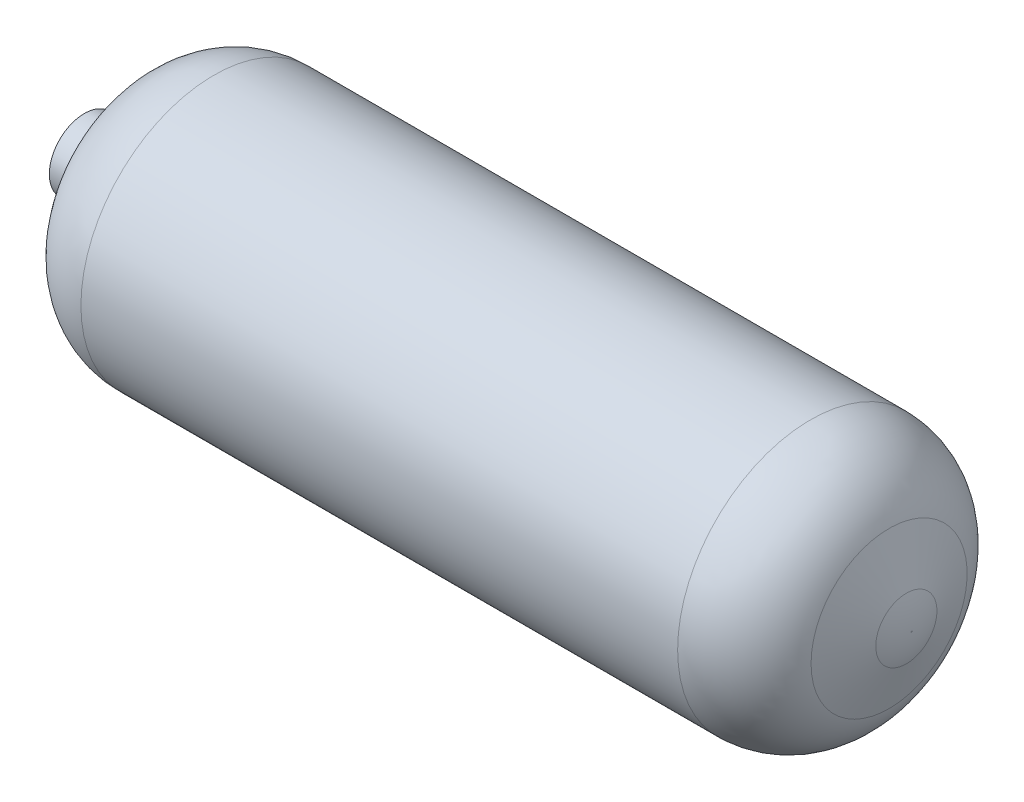
SolidWorks part; units mm, degrees
material "6061-T6 (SS)"
ref_plane "Front Plane" through (0, 0, 0) normal (0, 0, 1) x (1, 0, 0)
ref_plane "Top Plane" through (0, 0, 0) normal (0, 1, 0) x (1, 0, 0)
ref_plane "Right Plane" through (0, 0, 0) normal (1, 0, 0) x (0, 0, -1)
sketch "Sketch1" plane through (0, 0, 0) normal (0, 0, 1) x (1, 0, 0)
  line L0 (-0.2756, 0.129) -> (0.3032, 0.129)
  line L1 (-0.4012, 0.034) -> (-0.4012, 0)
  line L2 (-0.4012, 0.034) -> (-0.3773, 0.034)
  line L4 (-0.3729, 0.0367) -> (-0.3487, 0.0842)
  line L5 (-0.4012, 0) -> (0.4012, 0) construction
  line L6 (0.3794, 0.0757) -> (0.3961, 0.0297)
  line L7 (-0.4012, 0) -> (0.4012, 0)
  line L8 (0.4012, 0) -> (0.4012, 0.0006)
  arc A0 (-0.2756, 0.129) -> (-0.3487, 0.0842) centre (-0.2756, 0.047) ccw
  arc A1 (0.3032, 0.129) -> (0.3794, 0.0757) centre (0.3032, 0.048) cw
  arc A2 (0.4012, 0.0006) -> (0.3961, 0.0297) centre (0.3163, 0.0006) ccw
  arc A3 (-0.3729, 0.0367) -> (-0.3773, 0.034) centre (-0.3773, 0.039) cw
  point P6 (-0.3742, 0.034)
  dimension "D8" = 0.082
  dimension "D11" = 0.081
  dimension "D13" = 0.085
  dimension "D6" = 0.005
  dimension "D2" = 0.2756
  dimension "D3" = 0.034
  dimension "D4" = 0.3032
  dimension "D5" = 0.027
  dimension "D7" = 117
  dimension "D9" = 0.8025
  dimension "D10" = 110
revolve "Revolve2" add sketch "Sketch1" angle 360 about L7 region at (0.0088, 0.062, 0)
scale "Scale1" scale about origin uniform scaling yes scale factor 649.767462
shell "Shell2" thickness 5.588
sketch "Sketch2" plane through (0, 0, 0) normal (0, 1, 0) x (1, 0, 0)
  line L7 (246.4991, 49.1898) -> (257.3884, 19.2716)
  line L8 (260.7192, 0.3818) -> (197.042, 0.3818)
  line L9 (197.042, -83.82) -> (197.042, 83.82) construction
  line L10 (197.042, 0.3818) -> (197.042, 83.82)
  line L11 (-226.5465, 54.7281) -> (-242.2713, 23.8664)
  line L12 (-260.7192, 22.0921) -> (-245.1667, 22.0921)
  line L13 (-260.7192, 22.0921) -> (-260.7192, 0)
  line L14 (-260.7192, 22.0921) -> (-260.7192, -22.0921) construction
  line L15 (-260.7192, 0) -> (-179.0728, 0)
  line L16 (-179.0728, -83.82) -> (-179.0728, 83.82) construction
  line L17 (-179.0728, 0) -> (-179.0728, 83.82)
  arc A2 (197.042, 83.82) -> (246.4991, 49.1898) centre (197.042, 31.1888) cw
  arc A3 (257.3884, 19.2716) -> (260.7192, 0.3818) centre (205.489, 0.3818) cw
  arc A4 (-179.0728, 83.82) -> (-226.5465, 54.7281) centre (-179.0728, 30.5391) ccw
  arc A5 (-242.2713, 23.8664) -> (-245.1667, 22.0921) centre (-245.1667, 25.3417) cw
revolve "Added to make cavity cut for shoulder" [suppressed] add sketch "Sketch2" angle 360 about L15
